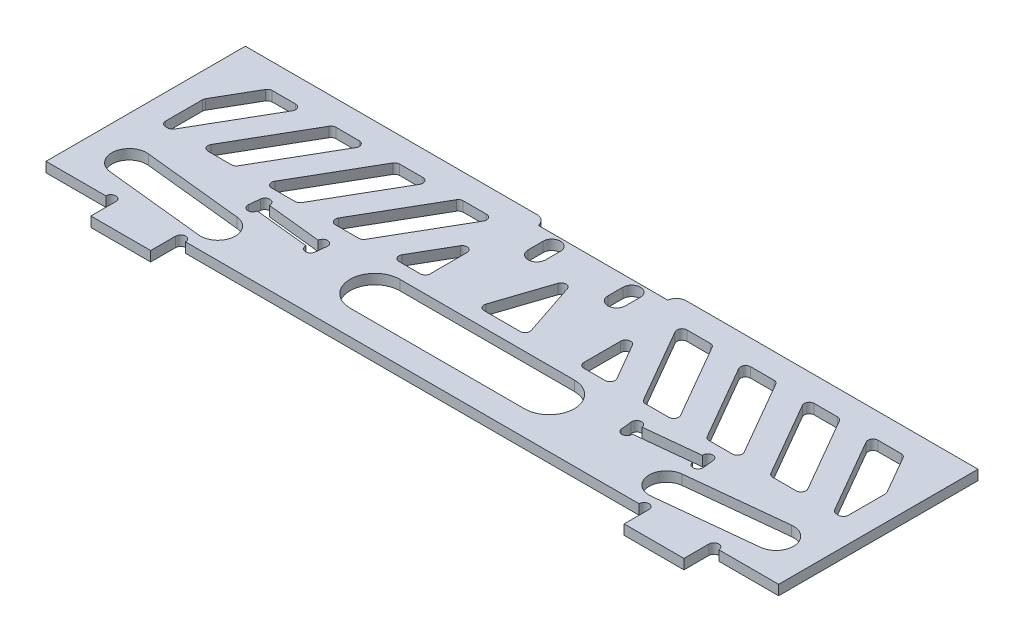
SolidWorks part; units mm, degrees
ref_plane "前视基准面" through (0, 0, 0) normal (0, 0, 1) x (1, 0, 0)
ref_plane "上视基准面" through (0, 0, 0) normal (0, 1, 0) x (1, 0, 0)
ref_plane "右视基准面" through (0, 0, 0) normal (1, 0, 0) x (0, 0, -1)
sketch "草图1" plane through (0, 0, 0) normal (0, 1, 0) x (1, 0, 0)
  line L1 (-73.5, 20) -> (73.5, 20)
  line L2 (-73.5, 20) -> (-73.5, -20)
  line L3 (-73.5, -20) -> (73.5, -20)
  line L4 (73.5, 20) -> (73.5, -20)
  line L5 (-73.5, 20) -> (73.5, -20) construction
  line L6 (-73.5, -20) -> (73.5, 20) construction
  point P0 (0, 0)
  dimension "D1" = 147
  dimension "D2" = 40
extrude "凸台-拉伸1" add sketch "草图1" along normal blind 2
sketch "草图2" plane through (0, 2, 0) normal (0, 1, 0) x (1, 0, 0)
  line L0 (-45.6587, -7.223) -> (-45.4288, -5.0351)
  line L1 (-45.4288, -5.0351) -> (-30.5109, -6.603)
  line L2 (-30.5109, -6.603) -> (-30.7409, -8.791)
  line L3 (-30.7409, -8.791) -> (-45.6587, -7.223)
  line L4 (-73.5, -20) -> (73.5, -20) construction
  dimension "D1" = 8.791
  dimension "D2" = 30.7409
  dimension "D3" = 15
  dimension "D4" = 2.2
  dimension "D5" = 6
extrude "切除-拉伸1" cut sketch "草图2" against normal through all
sketch "草图3" plane through (0, 2, 0) normal (0, 1, 0) x (1, 0, 0)
  line L0 (-30.5109, -6.603) -> (-45.4288, -5.0351) construction
  line L1 (-45.6587, -7.223) -> (-30.7409, -8.791) construction
  line L2 (-45.4288, -5.0351) -> (-45.6587, -7.223) construction
  line L3 (-30.7409, -8.791) -> (-30.5109, -6.603) construction
  circle A0 centre (-44.4342, -5.1396) radius 1
  circle A1 centre (-44.6642, -7.3276) radius 1
  circle A2 centre (-31.5055, -6.4985) radius 1
  circle A3 centre (-31.7354, -8.6864) radius 1
  dimension "D1" = 2
extrude "切除-拉伸2" cut sketch "草图3" against normal through all
mirror "镜向1" about plane through (0, 0, 0) normal (1, 0, 0) of "切除-拉伸1", "切除-拉伸2"
sketch "草图5" plane through (0, 0, 20) normal (0, 0, 1) x (1, 0, 0)
  line L0 (-73.5, 0) -> (73.5, 0) construction
  line L1 (59.5, 0) -> (47.5, 0)
  line L2 (59.5, 0) -> (59.5, 2)
  line L3 (59.5, 2) -> (47.5, 2)
  line L4 (47.5, 0) -> (47.5, 2)
  line L5 (-73.5, 2) -> (73.5, 2) construction
  line L6 (-73.5, 2) -> (-73.5, 0) construction
  line L7 (-59.5, 2) -> (-47.5, 2)
  line L8 (-59.5, 2) -> (-59.5, 0)
  line L9 (-59.5, 0) -> (-47.5, 0)
  line L10 (-47.5, 2) -> (-47.5, 0)
  line L11 (73.5, 2) -> (73.5, 0) construction
  dimension "D1" = 14
  dimension "D2" = 14
  dimension "D3" = 12
  dimension "D4" = 12
extrude "凸台-拉伸2" add sketch "草图5" along normal blind 5
sketch "草图7" plane through (0, 2, 0) normal (0, 1, 0) x (1, 0, 0)
  line L0 (59.5, -20) -> (73.5, -20) construction
  line L1 (-47.5, -20) -> (47.5, -20) construction
  line L2 (-73.5, -20) -> (-59.5, -20) construction
  line L3 (-59.5, -25) -> (-59.5, -20) construction
  line L4 (-47.5, -25) -> (-47.5, -20) construction
  line L5 (47.5, -25) -> (47.5, -20) construction
  line L6 (59.5, -25) -> (59.5, -20) construction
  circle A0 centre (60.5, -20) radius 1
  circle A1 centre (46.5, -20) radius 1
  circle A2 centre (-46.5, -20) radius 1
  circle A3 centre (-60.5, -20) radius 1
  dimension "D1" = 2
extrude "切除-拉伸3" cut sketch "草图7" against normal through all
sketch "草图10" plane through (0, 2, 0) normal (0, 1, 0) x (1, 0, 0)
  line L0 (-64.8904, -11.9094) -> (-45, -14) construction
  line L1 (-64.5246, -8.4286) -> (-44.6342, -10.5192)
  line L2 (-65.2563, -15.3903) -> (-45.3658, -17.4808)
  line L3 (-43.6697, -7.4321) -> (-32.7299, -8.5819) construction
  arc A0 (-64.5246, -8.4286) -> (-65.2563, -15.3903) centre (-64.8904, -11.9094) ccw
  arc A1 (-45.3658, -17.4808) -> (-44.6342, -10.5192) centre (-45, -14) ccw
  point P2 (-54.9452, -12.9547)
  dimension "D2" = 3.5
  dimension "D1" = 20
  dimension "D3" = 45
  dimension "D4" = 14
extrude "切除-拉伸5" cut sketch "草图10" against normal through all
mirror "镜向2" about plane through (0, 0, 0) normal (1, 0, 0) of "切除-拉伸5"
sketch "草图11" plane through (0, 2, 0) normal (0, 1, 0) x (1, 0, 0)
  line L0 (73.5, 20) -> (-73.5, 20) construction
  line L1 (-13, 21.75) -> (13, 21.75)
  line L2 (-13, 21.75) -> (-13, 18.25)
  line L3 (-13, 18.25) -> (13, 18.25)
  line L4 (13, 21.75) -> (13, 18.25)
  line L5 (-13, 21.75) -> (13, 18.25) construction
  line L6 (-13, 18.25) -> (13, 21.75) construction
  point P0 (0, 20)
  dimension "D1" = 3.5
  dimension "D2" = 26
extrude "切除-拉伸6" cut sketch "草图11" against normal blind 10
fillet "圆角1" radius 2 2 edges at (13, 1, -20) (-13, 1, -20)
sketch "草图12" plane through (0, 2, 0) normal (0, 1, 0) x (1, 0, 0)
  line L0 (-8, 16) -> (-8, 13) construction
  line L1 (-6.25, 16) -> (-6.25, 13)
  line L2 (-9.75, 16) -> (-9.75, 13)
  line L3 (8, 16) -> (8, 13) construction
  line L4 (9.75, 16) -> (9.75, 13)
  line L5 (6.25, 16) -> (6.25, 13)
  line L6 (8, 16) -> (-8, 16) construction
  arc A0 (-6.25, 16) -> (-9.75, 16) centre (-8, 16) ccw
  arc A1 (-9.75, 13) -> (-6.25, 13) centre (-8, 13) ccw
  arc A2 (9.75, 16) -> (6.25, 16) centre (8, 16) ccw
  arc A3 (6.25, 13) -> (9.75, 13) centre (8, 13) ccw
  point P2 (-8, 14.5)
  point P7 (8, 14.5)
  dimension "D1" = 1.75
  dimension "D2" = 16
  dimension "D3" = 16
  dimension "D4" = 8
  dimension "D5" = 3
extrude "切除-拉伸7" cut sketch "草图12" against normal through all
sketch "草图13" plane through (0, 2, 0) normal (0, 1, 0) x (1, 0, 0)
  line L0 (0, 0) -> (0, -50000) construction
  line L1 (-17.5, -10) -> (17.5, -10) construction
  line L2 (-17.5, -5) -> (17.5, -5)
  line L3 (-17.5, -15) -> (17.5, -15)
  line L4 (-45.5, -20) -> (45.5, -20) construction
  line L5 (0, 13) -> (-5, -2)
  line L6 (-5, -2) -> (5, -2)
  line L7 (5, -2) -> (0, 13)
  arc A0 (-17.5, -5) -> (-17.5, -15) centre (-17.5, -10) ccw
  arc A1 (17.5, -15) -> (17.5, -5) centre (17.5, -10) ccw
  point P5 (0, -10)
  point P15 (0, 0)
  point P16 (-5, -3.1152)
  dimension "D2" = 5
  dimension "D1" = 5
  dimension "D3" = 35
  dimension "D4" = 10
  dimension "D5" = 15
  dimension "D6" = 3
extrude "切除-拉伸8" cut sketch "草图13" against normal blind 10
fillet "圆角2" radius 1 3 edges at (0, 1, -13) (5, 1, 2) (-5, 1, 2)
sketch "草图14" plane through (0, 2, 0) normal (0, 1, 0) x (1, 0, 0)
  line L0 (-63.685, 15) -> (-73.5, -2)
  line L1 (-73.5, -2) -> (-66.5, -2)
  line L2 (-66.5, -2) -> (-56.685, 15)
  line L3 (-56.685, 15) -> (-63.685, 15)
  line L4 (-68.5, 20) -> (-68.5, -20)
  line L5 (-14.9843, 20) -> (-73.5, 20) construction
  line L6 (-73.5, -20) -> (-61.5, -20) construction
  line L7 (-73.5, 20) -> (-73.5, -20) construction
  line L8 (-43.9115, 15) -> (-50.9115, 15)
  line L9 (-50.9115, 15) -> (-60.7265, -2)
  line L10 (-60.7265, -2) -> (-53.7265, -2)
  line L11 (-53.7265, -2) -> (-43.9115, 15)
  line L12 (-31.138, 15) -> (-38.138, 15)
  line L13 (-38.138, 15) -> (-47.953, -2)
  line L14 (-47.953, -2) -> (-40.953, -2)
  line L15 (-40.953, -2) -> (-31.138, 15)
  line L16 (-18.3645, 15) -> (-25.3645, 15)
  line L17 (-25.3645, 15) -> (-35.1795, -2)
  line L18 (-35.1795, -2) -> (-28.1795, -2)
  line L19 (-28.1795, -2) -> (-18.3645, 15)
  line L21 (-15.406, 10.1244) -> (-22.406, -2)
  line L22 (-22.406, -2) -> (-15.406, -2)
  line L25 (0.1825, 15) -> (0, 14.684)
  line L40 (0, 0) -> (0, -50000) construction
  line L41 (-15.406, -2) -> (-15.406, 10.1244)
  line L42 (68.5, 20) -> (68.5, -20)
  line L43 (-5.591, 15) -> (-12.591, 15) [skipped]
  line L44 (-15.406, -2) -> (-5.591, 15) [skipped]
  line L45 (35.688, -2) -> (45.503, 15) [skipped]
  line L46 (38.503, 15) -> (28.688, -2) [skipped]
  line L47 (22.9145, -2) -> (32.7295, 15) [skipped]
  line L48 (45.503, 15) -> (38.503, 15) [skipped]
  line L49 (28.688, -2) -> (35.688, -2) [skipped]
  line L50 (25.7295, 15) -> (15.9145, -2) [skipped]
  line L51 (32.7295, 15) -> (25.7295, 15) [skipped]
  line L52 (15.9145, -2) -> (22.9145, -2) [skipped]
  line L53 (10.141, -2) -> (19.956, 15) [skipped]
  line L54 (12.956, 15) -> (3.141, -2) [skipped]
  line L55 (3.141, -2) -> (10.141, -2) [skipped]
  line L56 (19.956, 15) -> (12.956, 15) [skipped]
  line L57 (7.1825, 15) -> (0.1825, 15) [skipped]
  line L58 (-2.6325, -2) -> (0, 2.5596) [skipped]
  line L59 (-9.6325, -2) -> (-2.6325, -2) [skipped]
  line L60 (15.406, -2) -> (15.406, 10.1244)
  line L61 (22.406, -2) -> (15.406, -2)
  line L62 (15.406, 10.1244) -> (22.406, -2)
  line L63 (28.1795, -2) -> (18.3645, 15)
  line L64 (35.1795, -2) -> (28.1795, -2)
  line L65 (25.3645, 15) -> (35.1795, -2)
  line L66 (18.3645, 15) -> (25.3645, 15)
  line L67 (47.953, -2) -> (40.953, -2)
  line L68 (38.138, 15) -> (47.953, -2)
  line L69 (31.138, 15) -> (38.138, 15)
  line L70 (53.7265, -2) -> (43.9115, 15)
  line L71 (60.7265, -2) -> (53.7265, -2)
  line L72 (50.9115, 15) -> (60.7265, -2)
  line L73 (43.9115, 15) -> (50.9115, 15)
  line L74 (56.685, 15) -> (63.685, 15)
  line L75 (66.5, -2) -> (56.685, 15)
  line L76 (73.5, -2) -> (66.5, -2)
  line L77 (63.685, 15) -> (73.5, -2)
  line L78 (40.953, -2) -> (31.138, 15)
  dimension "D1" = 5
  dimension "D2" = 60
  dimension "D3" = 5
  dimension "D4" = 18
  dimension "D5" = 7
  dimension "D7" = 5
  dimension "D6" = 9
extrude "切除-拉伸9" cut sketch "草图14" against normal blind 10 contours L0 L4 L1 L2 L3 | L10 L11 L8 L9 | L14 L15 L12 L13 | L18 L19 L16 L17 | L22 L41 L21 | L62 L60 L61 | L66 L63 L64 L65 | L78 L67 L68 L69 | L73 L70 L71 L72 | L77 L74 L75 L76 L42
fillet "圆角3" radius 1 40 edges at (63.685, 1, -15) (56.685, 1, -15) (66.5, 1, 2) (68.5, 1, 2) (68.5, 1, -6.6603) (43.9115, 1, -15) (53.7265, 1, 2) (60.7265, 1, 2) (50.9115, 1, -15) (40.953, 1, 2) (47.953, 1, 2) (38.138, 1, -15) (31.138, 1, -15) (18.3645, 1, -15) (28.1795, 1, 2) (35.1795, 1, 2) (25.3645, 1, -15) (15.406, 1, -10.1244) (15.406, 1, 2) (22.406, 1, 2) (-15.406, 1, 2) (-15.406, 1, -10.1244) (-22.406, 1, 2) (-28.1795, 1, 2) (-18.3645, 1, -15) (-25.3645, 1, -15) (-35.1795, 1, 2) (-40.953, 1, 2) (-31.138, 1, -15) (-38.138, 1, -15) (-47.953, 1, 2) (-43.9115, 1, -15) (-50.9115, 1, -15) (-60.7265, 1, 2) (-68.5, 1, -6.6603) (-68.5, 1, 2) (-66.5, 1, 2) (-56.685, 1, -15) (-63.685, 1, -15) (-53.7265, 1, 2)
